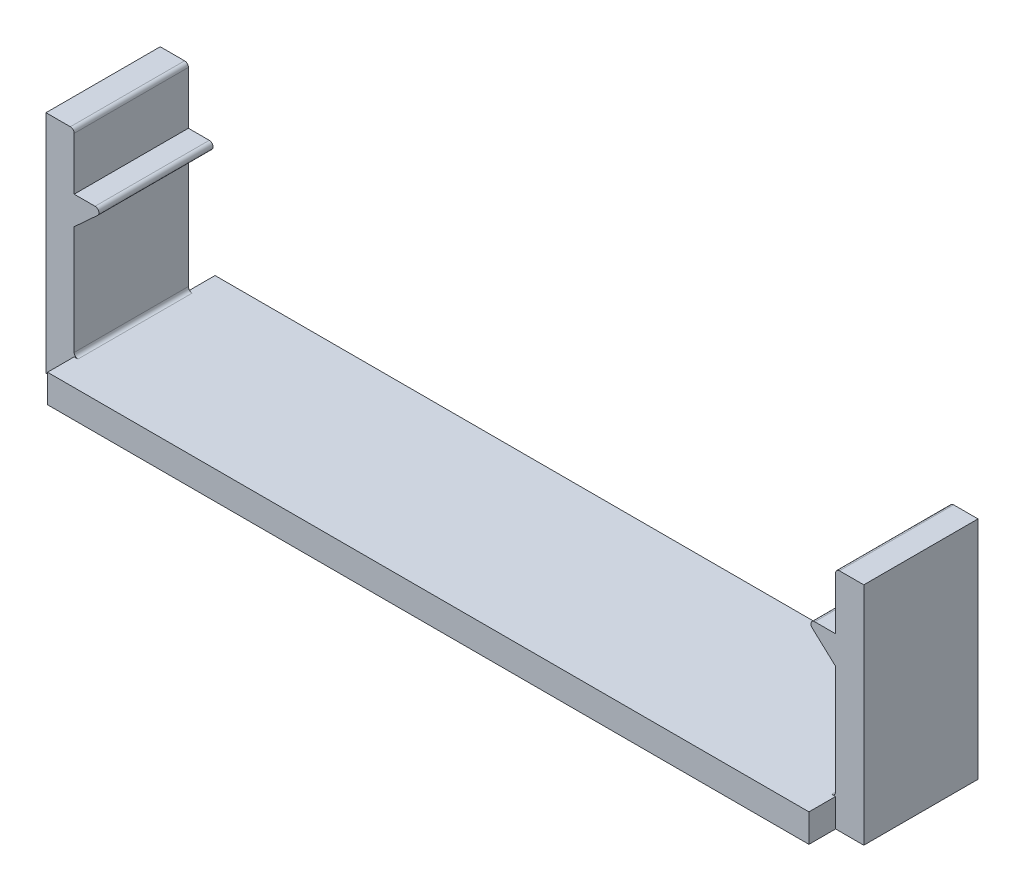
SolidWorks part; units mm, degrees
ref_plane "Front Plane" through (0, 0, 0) normal (0, 0, 1) x (1, 0, 0)
ref_plane "Top Plane" through (0, 0, 0) normal (0, 1, 0) x (1, 0, 0)
ref_plane "Right Plane" through (0, 0, 0) normal (1, 0, 0) x (0, 0, -1)
sketch "Clips Outline" plane through (0, 0, 0) normal (0, 0, 1) x (1, 0, 0)
  line L0 (12.7, 3.7592) -> (11.677, 4.699)
  line L1 (-12.7, 0) -> (-12.7, 3.7592)
  line L2 (12.7, 4.699) -> (12.7, 6.5837)
  line L3 (-12.7, 6.5837) -> (-13.6398, 6.5837)
  line L4 (-13.6398, 6.5837) -> (-13.6398, -0.9398)
  line L5 (-13.6398, -0.9398) -> (-12.7, -0.9398)
  line L6 (-12.7, 0) -> (-12.7, -0.9398)
  line L7 (-12.7, 4.699) -> (-11.677, 4.699)
  line L8 (-12.7, 4.699) -> (-12.7, 6.5837)
  line L9 (-12.7, 3.7592) -> (-11.677, 4.699)
  line L10 (0, 0) -> (0, 10.8923) construction
  line L11 (12.7, 4.699) -> (11.677, 4.699)
  line L12 (12.7, 0) -> (12.7, -0.9398)
  line L13 (13.6398, -0.9398) -> (12.7, -0.9398)
  line L14 (13.6398, 6.5837) -> (13.6398, -0.9398)
  line L15 (12.7, 6.5837) -> (13.6398, 6.5837)
  line L16 (12.7, 0) -> (12.7, 3.7592)
  point P3 (0, 0)
  dimension "D1" = 12.7
extrude "Clips" add sketch "Clips Outline" along normal mid plane 3.81
sketch "Base Outline Adhesive" plane through (0, 0, 0) normal (0, 0, 1) x (1, 0, 0)
  line L0 (12.7, 0) -> (-12.7, 0)
  line L1 (-12.7, -0.9398) -> (12.7, -0.9398)
  line L2 (12.7, -0.9398) -> (12.7, 0)
  line L3 (-12.7, 0) -> (-12.7, -0.9398)
  point P3 (0, 0)
extrude "Adhesive Base" add sketch "Base Outline Adhesive" along normal mid plane 5.588
fillet "Fillet2" radius 0.127 6 edges at (12.7, 0, 0) (-12.7, 0, 0) (12.7, 6.5837, 0) (-12.7, 6.5837, 0) (11.677, 4.699, 0) (-11.677, 4.699, 0)
sketch3d "Ribbon Cable Axis Location"
  line L0 (12.7, 2.54, 1.905) -> (-12.7, 2.54, 1.905) construction
  line L1 (0, 2.54, -1.905) -> (0, 2.54, 1.905) construction
  line L2 (12.7, 2.54, -1.905) -> (-12.7, 2.54, -1.905) construction
  line L4 (-12.7, 0.127, 1.905) -> (-12.7, 3.7592, 1.905) construction
  line L5 (12.7, 3.7592, 1.905) -> (12.7, 0.127, 1.905) construction
  line L6 (12.7, 3.7592, -1.905) -> (12.7, 0.127, -1.905) construction
  line L7 (-12.7, 0.127, -1.905) -> (-12.7, 3.7592, -1.905) construction
  line L8 (-12.7, -0.4699, 1.905) -> (-12.7, 1.1592, 1.905) construction
  line L9 (-12.7, -0.4699, -1.905) -> (-12.7, 1.2284, -1.905) construction
  line L10 (12.7, 1.0242, 1.905) -> (12.7, -0.008, 1.905) construction
  line L11 (12.7, 0.9086, -1.905) -> (12.7, 0.0008, -1.905) construction
  point P5 (0, 2.54, -1.905)
  point P6 (0, 2.54, 1.905)
ref_axis "Ribbon Cable Axis" through (0, 2.54, -1.905) along (0, 0, 1)
equation "\"D1@Clips Outline\" = \"Base_Width@Base Outline Adhesive\"/2"
